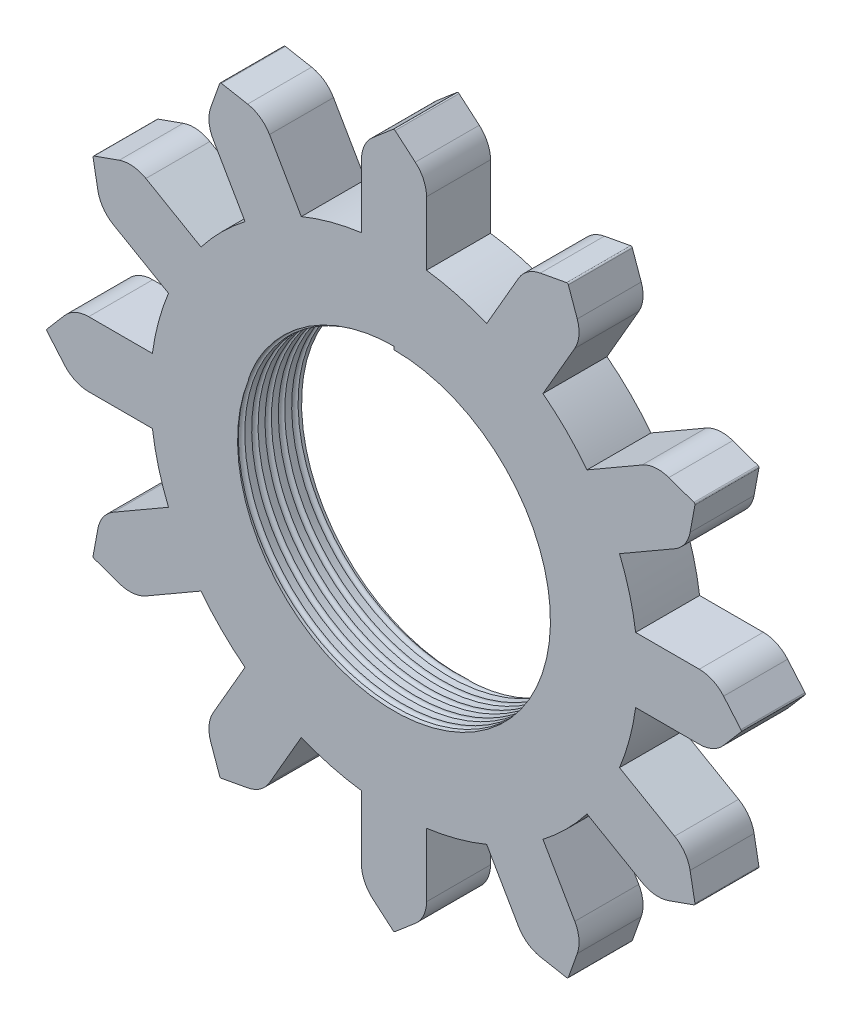
SolidWorks part; units mm, degrees
ref_plane "Front Plane" through (0, 0, 0) normal (0, 0, 1) x (1, 0, 0)
ref_plane "Top Plane" through (0, 0, 0) normal (0, 1, 0) x (1, 0, 0)
ref_plane "Right Plane" through (0, 0, 0) normal (1, 0, 0) x (0, 0, -1)
sketch "Sketch1" plane through (0, 0, 0) normal (0, 0, 1) x (1, 0, 0)
  line L0 (-0.0649, 21.6846) -> (-1.3306, 20.6039)
  line L1 (-2.032, 19.0829) -> (-2.032, 15.1039)
  line L2 (0, 21.74) -> (0, 15.24) construction
  line L3 (0.0649, 21.6846) -> (1.3306, 20.6039)
  line L4 (2.032, 19.0829) -> (2.032, 15.1039)
  line L5 (10.8985, 18.7469) -> (11.4543, 17.1782)
  line L6 (10.786, 18.8118) -> (9.1496, 18.5088)
  line L7 (11.3012, 15.5103) -> (9.3117, 12.0644)
  line L8 (7.7817, 17.5423) -> (5.7922, 14.0964)
  line L9 (18.8118, 10.786) -> (18.5088, 9.1496)
  line L10 (18.7469, 10.8985) -> (17.1782, 11.4543)
  line L11 (17.5423, 7.7817) -> (14.0964, 5.7922)
  line L12 (15.5103, 11.3012) -> (12.0644, 9.3117)
  line L13 (21.6846, -0.0649) -> (20.6039, -1.3306)
  line L14 (21.6846, 0.0649) -> (20.6039, 1.3306)
  line L15 (19.0829, -2.032) -> (15.1039, -2.032)
  line L16 (19.0829, 2.032) -> (15.1039, 2.032)
  line L17 (18.7469, -10.8985) -> (17.1782, -11.4543)
  line L18 (18.8118, -10.786) -> (18.5088, -9.1496)
  line L19 (15.5103, -11.3012) -> (12.0644, -9.3117)
  line L20 (-2.032, -6.4991) -> (-2.032, -2.5202)
  line L21 (17.5423, -7.7817) -> (14.0964, -5.7922)
  line L22 (10.786, -18.8118) -> (9.1496, -18.5088)
  line L23 (10.8985, -18.7469) -> (11.4543, -17.1782)
  line L24 (7.7817, -17.5423) -> (5.7922, -14.0964)
  line L25 (11.3012, -15.5103) -> (9.3117, -12.0644)
  line L26 (-0.0649, -21.6846) -> (-1.3306, -20.6039)
  line L27 (0.0649, -21.6846) -> (1.3306, -20.6039)
  line L28 (-2.032, -19.0829) -> (-2.032, -15.1039)
  line L29 (2.032, -19.0829) -> (2.032, -15.1039)
  line L30 (-10.8985, -18.7469) -> (-11.4543, -17.1782)
  line L31 (-10.786, -18.8118) -> (-9.1496, -18.5088)
  line L32 (-11.3012, -15.5103) -> (-9.3117, -12.0644)
  line L33 (-7.7817, -17.5423) -> (-5.7922, -14.0964)
  line L34 (-18.8118, -10.786) -> (-18.5088, -9.1496)
  line L35 (-18.7469, -10.8985) -> (-17.1782, -11.4543)
  line L36 (-17.5423, -7.7817) -> (-14.0964, -5.7922)
  line L37 (-15.5103, -11.3012) -> (-12.0644, -9.3117)
  line L38 (-21.6846, 0.0649) -> (-20.6039, 1.3306)
  line L39 (-21.6846, -0.0649) -> (-20.6039, -1.3306)
  line L40 (-19.0829, 2.032) -> (-15.1039, 2.032)
  line L41 (-19.0829, -2.032) -> (-15.1039, -2.032)
  line L42 (-18.7469, 10.8985) -> (-17.1782, 11.4543)
  line L43 (-18.8118, 10.786) -> (-18.5088, 9.1496)
  line L44 (-15.5103, 11.3012) -> (-12.0644, 9.3117)
  line L45 (-17.5423, 7.7817) -> (-14.0964, 5.7922)
  line L46 (-10.786, 18.8118) -> (-9.1496, 18.5088)
  line L47 (-10.8985, 18.7469) -> (-11.4543, 17.1782)
  line L48 (-7.7817, 17.5423) -> (-5.7922, 14.0964)
  line L49 (-11.3012, 15.5103) -> (-9.3117, 12.0644)
  line L67 (2.032, -6.4991) -> (2.032, -2.5202) [skipped]
  line L70 (0.0649, -9.1008) -> (1.3306, -8.0202) [skipped]
  line L71 (-0.0649, -9.1008) -> (-1.3306, -8.0202) [skipped]
  circle A0 centre (0, 0) radius 9.779
  circle A1 centre (0, 0) radius 15.24
  arc A2 (2.032, 19.0829) -> (1.3306, 20.6039) centre (0.032, 19.0829) ccw
  arc A3 (-2.032, 19.0829) -> (-1.3306, 20.6039) centre (-0.032, 19.0829) cw
  arc A4 (0.0649, 21.6846) -> (-0.0649, 21.6846) centre (0, 21.6085) ccw
  circle A5 centre (0, 0) radius 15.24
  arc A6 (10.8985, 18.7469) -> (10.786, 18.8118) centre (10.8043, 18.7135) ccw
  arc A7 (7.7817, 17.5423) -> (9.1496, 18.5088) centre (9.5137, 16.5423) cw
  arc A8 (11.3012, 15.5103) -> (11.4543, 17.1782) centre (9.5692, 16.5103) ccw
  circle A9 centre (0, 0) radius 15.24
  arc A10 (18.8118, 10.786) -> (18.7469, 10.8985) centre (18.7135, 10.8043) ccw
  arc A11 (15.5103, 11.3012) -> (17.1782, 11.4543) centre (16.5103, 9.5692) cw
  arc A12 (17.5423, 7.7817) -> (18.5088, 9.1496) centre (16.5423, 9.5137) ccw
  circle A13 centre (0, 0) radius 15.24
  arc A14 (21.6846, -0.0649) -> (21.6846, 0.0649) centre (21.6085, 0) ccw
  arc A15 (19.0829, 2.032) -> (20.6039, 1.3306) centre (19.0829, 0.032) cw
  arc A16 (19.0829, -2.032) -> (20.6039, -1.3306) centre (19.0829, -0.032) ccw
  circle A17 centre (0, 0) radius 15.24
  arc A18 (18.7469, -10.8985) -> (18.8118, -10.786) centre (18.7135, -10.8043) ccw
  arc A19 (17.5423, -7.7817) -> (18.5088, -9.1496) centre (16.5423, -9.5137) cw
  arc A20 (15.5103, -11.3012) -> (17.1782, -11.4543) centre (16.5103, -9.5692) ccw
  circle A21 centre (0, 0) radius 15.24
  arc A22 (10.786, -18.8118) -> (10.8985, -18.7469) centre (10.8043, -18.7135) ccw
  arc A23 (11.3012, -15.5103) -> (11.4543, -17.1782) centre (9.5692, -16.5103) cw
  arc A24 (7.7817, -17.5423) -> (9.1496, -18.5088) centre (9.5137, -16.5423) ccw
  circle A25 centre (0, 0) radius 15.24
  arc A26 (-0.0649, -21.6846) -> (0.0649, -21.6846) centre (0, -21.6085) ccw
  arc A27 (2.032, -19.0829) -> (1.3306, -20.6039) centre (0.032, -19.0829) cw
  arc A28 (-2.032, -19.0829) -> (-1.3306, -20.6039) centre (-0.032, -19.0829) ccw
  circle A29 centre (0, 0) radius 15.24
  arc A30 (-10.8985, -18.7469) -> (-10.786, -18.8118) centre (-10.8043, -18.7135) ccw
  arc A31 (-7.7817, -17.5423) -> (-9.1496, -18.5088) centre (-9.5137, -16.5423) cw
  arc A32 (-11.3012, -15.5103) -> (-11.4543, -17.1782) centre (-9.5692, -16.5103) ccw
  circle A33 centre (0, 0) radius 15.24
  arc A34 (-18.8118, -10.786) -> (-18.7469, -10.8985) centre (-18.7135, -10.8043) ccw
  arc A35 (-15.5103, -11.3012) -> (-17.1782, -11.4543) centre (-16.5103, -9.5692) cw
  arc A36 (-17.5423, -7.7817) -> (-18.5088, -9.1496) centre (-16.5423, -9.5137) ccw
  circle A37 centre (0, 0) radius 15.24
  arc A38 (-21.6846, 0.0649) -> (-21.6846, -0.0649) centre (-21.6085, 0) ccw
  arc A39 (-19.0829, -2.032) -> (-20.6039, -1.3306) centre (-19.0829, -0.032) cw
  arc A40 (-19.0829, 2.032) -> (-20.6039, 1.3306) centre (-19.0829, 0.032) ccw
  circle A41 centre (0, 0) radius 15.24
  arc A42 (-18.7469, 10.8985) -> (-18.8118, 10.786) centre (-18.7135, 10.8043) ccw
  arc A43 (-17.5423, 7.7817) -> (-18.5088, 9.1496) centre (-16.5423, 9.5137) cw
  arc A44 (-15.5103, 11.3012) -> (-17.1782, 11.4543) centre (-16.5103, 9.5692) ccw
  circle A45 centre (0, 0) radius 15.24
  arc A46 (-10.786, 18.8118) -> (-10.8985, 18.7469) centre (-10.8043, 18.7135) ccw
  arc A47 (-11.3012, 15.5103) -> (-11.4543, 17.1782) centre (-9.5692, 16.5103) cw
  arc A48 (-7.7817, 17.5423) -> (-9.1496, 18.5088) centre (-9.5137, 16.5423) ccw
  arc A53 (2.032, -6.4991) -> (1.3306, -8.0202) centre (0.032, -6.4991) cw [skipped]
  arc A54 (-2.032, -6.4991) -> (-1.3306, -8.0202) centre (-0.032, -6.4991) ccw [skipped]
  arc A56 (-0.0649, -9.1008) -> (0.0649, -9.1008) centre (0, -9.0247) ccw [skipped]
  point P12 (2.032, 20.0051)
  point P15 (-2.032, 20.0051)
  point P156 (0, 0)
  dimension "D1" = 30.48
  dimension "D2" = 19.558
  dimension "D6" = 2
  dimension "D7" = 0.1
  dimension "D3" = 6.5
  dimension "D4" = 2.032
  dimension "D5" = 5.5
  dimension "D8" = 2
  dimension "D9" = 12
extrude "Boss-Extrude1" add sketch "Sketch1" along normal blind 4
sketch "Sketch2" plane through (0, 0, 0) normal (0, 0, 1) x (1, 0, 0)
  circle A0 centre (0, 0) radius 9.779
  dimension "D1" = 19.558
curve "Helix/Spiral1" pitch 0.8333 height 3.9583 turns 4.75
sketch "Sketch4" plane through (0, 0, 0) normal (1, 0, 0) x (0, 0, -1)
  circle A0 centre (-0.2083, -9.779) radius 0.2
  dimension "D1" = 0.4
sweep "Cut-Sweep8" cut profiles "Sketch4" path "Helix/Spiral1"
